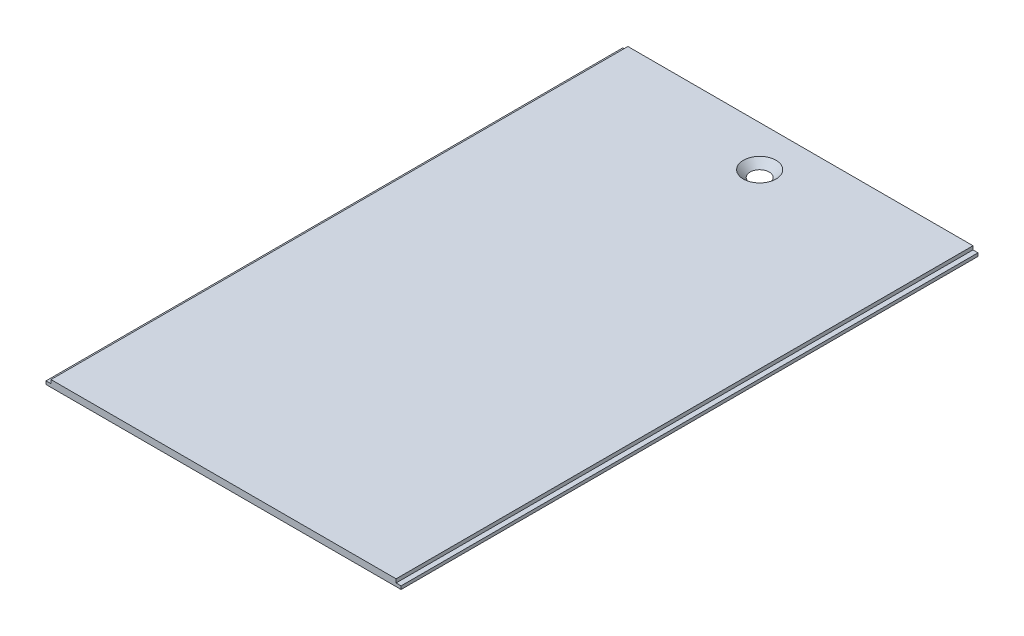
SolidWorks part; units mm, degrees
material "PLA"
ref_plane "Спереди" through (0, 0, 0) normal (0, 0, 1) x (1, 0, 0)
ref_plane "Сверху" through (0, 0, 0) normal (0, 1, 0) x (1, 0, 0)
ref_plane "Справа" through (0, 0, 0) normal (1, 0, 0) x (0, 0, -1)
sketch "Эскиз1" plane through (0, 0, 0) normal (0, 1, 0) x (1, 0, 0)
  line L1 (38.075, 63.65) -> (-38.075, 63.65)
  line L2 (38.075, 63.65) -> (38.075, -63.65)
  line L3 (38.075, -63.65) -> (-38.075, -63.65)
  line L4 (-38.075, 63.65) -> (-38.075, -63.65)
  line L5 (38.075, 63.65) -> (-38.075, -63.65) construction
  line L6 (38.075, -63.65) -> (-38.075, 63.65) construction
  point P0 (0, 0)
  dimension "D1" = 76.15
  dimension "D2" = 127.3
extrude "Бобышка-Вытянуть1" add sketch "Эскиз1" along normal blind 1.5
sketch "Эскиз2" plane through (0, 0, 63.65) normal (0, 0, 1) x (1, 0, 0)
  line L0 (0, 0) -> (0, -50000) construction
  line L1 (-38.075, 0) -> (-39.175, 0)
  line L2 (-38.075, 0) -> (-38.075, 0.7)
  line L3 (-38.075, 0.7) -> (-39.175, 0.7)
  line L4 (-39.175, 0) -> (-39.175, 0.7)
  line L5 (38.075, 0.7) -> (39.175, 0.7)
  line L6 (39.175, 0) -> (39.175, 0.7)
  line L7 (38.075, 0) -> (39.175, 0)
  line L8 (38.075, 0) -> (38.075, 0.7)
  dimension "D1" = 0.7
  dimension "D2" = 1.1
extrude "Бобышка-Вытянуть2" add sketch "Эскиз2" against normal up to surface (127.3 mm away) up to face at (0, 0.75, -63.65)
sketch "Эскиз3" plane through (0, 1.5, 0) normal (0, 1, 0) x (1, 0, 0)
  line L0 (0, 0) -> (0, 50000) construction
  line L1 (38.075, 63.65) -> (-38.075, 63.65) construction
  circle A0 centre (0, 54.65) radius 1.6
  dimension "D1" = 3.2
  dimension "D2" = 9
extrude "Вырез-Вытянуть1" cut sketch "Эскиз3" against normal through all
chamfer "Фаска1" distance 2 angle 45 1 edges at (0, 1.5, -53.05)
